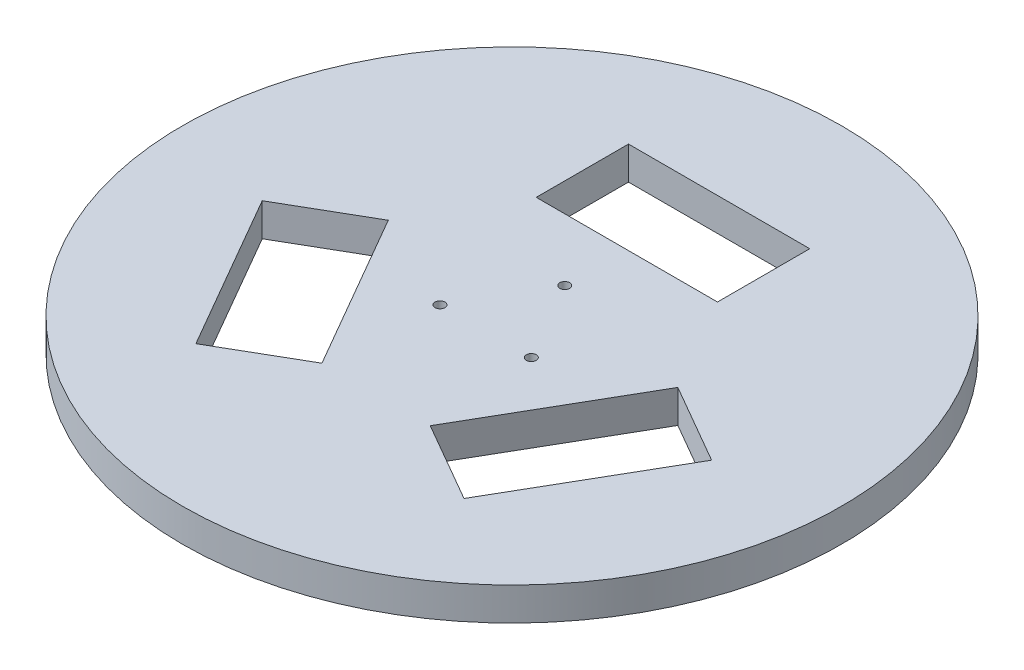
SolidWorks part; units mm, degrees
ref_plane "Front Plane" through (0, 0, 0) normal (0, 0, 1) x (1, 0, 0)
ref_plane "Top Plane" through (0, 0, 0) normal (0, 1, 0) x (1, 0, 0)
ref_plane "Right Plane" through (0, 0, 0) normal (1, 0, 0) x (0, 0, -1)
sketch "Sketch2" plane through (0, 0, 0) normal (0, 1, 0) x (1, 0, 0)
  line L0 (0, -68.0098) -> (0, 65.7503) construction
  line L1 (-27.5, 62.8517) -> (27.5, 62.8517)
  line L2 (-27.5, 62.8517) -> (-27.5, 34.8517)
  line L3 (-27.5, 34.8517) -> (27.5, 34.8517)
  line L4 (27.5, 62.8517) -> (27.5, 34.8517)
  line L5 (-27.5, 62.8517) -> (27.5, 34.8517) construction
  line L6 (-27.5, 34.8517) -> (27.5, 62.8517) construction
  line L7 (-70.2148, 0) -> (95.7201, 0) construction
  line L8 (0, 0) -> (-72.5813, -41.9048) construction
  line L9 (0, 0) -> (72.5813, -41.9048) construction
  line L10 (68.1811, -7.6101) -> (40.6811, -55.2415)
  line L11 (43.9324, 6.3899) -> (16.4324, -41.2415)
  line L12 (68.1811, -7.6101) -> (43.9324, 6.3899)
  line L13 (40.6811, -55.2415) -> (16.4324, -41.2415)
  line L14 (-40.6811, -55.2415) -> (-68.1811, -7.6101)
  line L15 (-16.4324, -41.2415) -> (-43.9324, 6.3899)
  line L16 (-40.6811, -55.2415) -> (-16.4324, -41.2415)
  line L17 (-68.1811, -7.6101) -> (-43.9324, 6.3899)
  circle A0 centre (0, 0) radius 100
  circle A1 centre (0, 16) radius 1.5
  circle A2 centre (0, 0) radius 16 construction
  circle A3 centre (13.8564, -8) radius 1.5
  circle A4 centre (-13.8564, -8) radius 1.5
  point P6 (0, 48.8517)
  point P13 (0, 0)
  point P33 (0, 0)
  dimension "D1" = 200
  dimension "D2" = 3
  dimension "D3" = 32
  dimension "D5" = 55
  dimension "D6" = 120
  dimension "D7" = 28
  dimension "D4" = 3
  dimension "D8" = 3
extrude "Boss-Extrude1" add sketch "Sketch2" along normal blind 10
ref_plane "Plane1" through (0, 20, 0) normal (0, 1, 0) x (1, 0, 0)
sketch "Sketch3" plane through (0, 20, 0) normal (0, 1, 0) x (1, 0, 0)
  circle A0 centre (0, 0) radius 100
  dimension "D1" = 200
